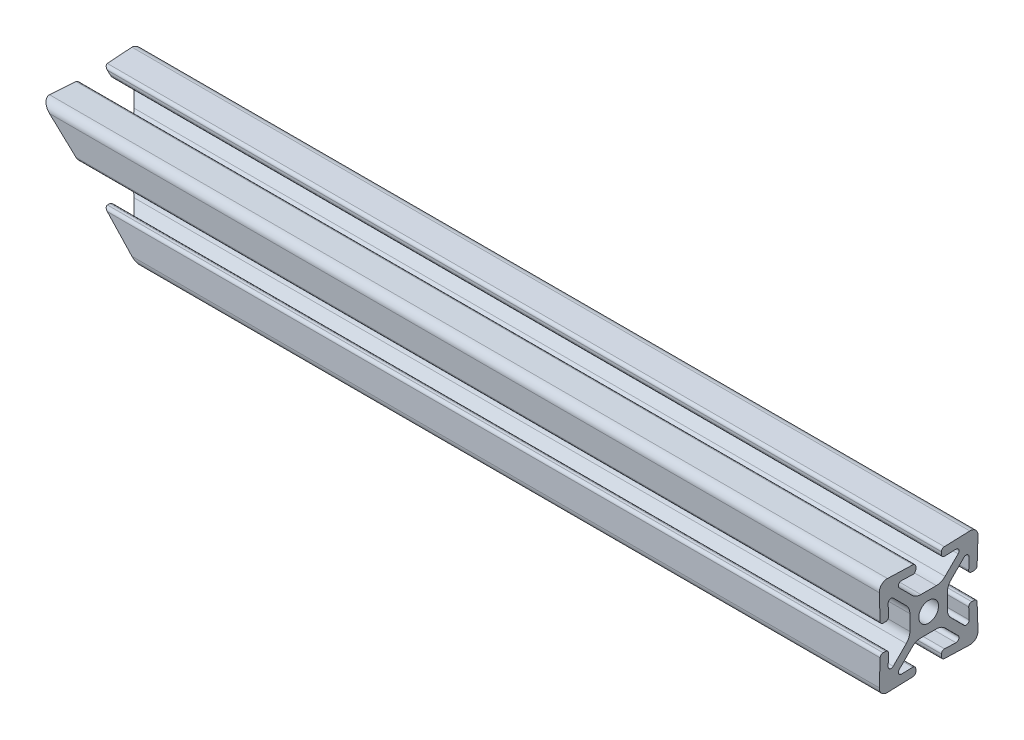
SolidWorks part; units mm, degrees
ref_plane "Front Plane" through (0, 0, 0) normal (0, 0, 1) x (1, 0, 0)
ref_plane "Top Plane" through (0, 0, 0) normal (0, 1, 0) x (1, 0, 0)
ref_plane "Right Plane" through (0, 0, 0) normal (1, 0, 0) x (0, 0, -1)
sketch "Sketch1" plane through (0, 0, 0) normal (1, 0, 0) x (0, 0, -1)
  line L0 (0, -12.7) -> (0, 12.7) construction
  line L1 (-7.874, 12.7) -> (7.874, 12.7) construction
  line L2 (-12.7, 0) -> (12.7, 0) construction
  line L3 (-7.874, 12.7) -> (-7.874, 4.826) construction
  line L4 (-3.302, 12.7) -> (3.302, 12.7) construction
  line L5 (-12.7, -12.7) -> (12.7, -12.7) construction
  line L6 (-12.7, 12.7) -> (12.7, 12.7) construction
  circle A0 centre (0, 0) radius 2.54 construction
  point P7 (0, 12.7)
  point P10 (0, 0)
  point P13 (0, 0)
  point P16 (0, 12.7)
  point P17 (-3.302, 12.7)
  point P18 (3.302, 12.7)
  point P21 (0, -12.7)
  point P24 (0, 12.7)
  dimension "Center Hole Diameter" = 5.08
  dimension "Rail Width" = 25.4
  dimension "Rail Height" = 25.4
  dimension "T-Slot Depth" = 7.874
  dimension "D1" = 15.748
  dimension "T-Slot Width" = 6.604
  dimension "D2" = 12.7
sketch "Sketch2" plane through (0, 0, 0) normal (0, 0, 1) x (1, 0, 0)
  line L0 (-107.7631, 0) -> (107.7631, 0) construction
  line L1 (0, 0) -> (0, 26.104) construction
  line L2 (107.7631, -12.7) -> (107.7631, 12.7) construction
  line L3 (-107.7631, -12.7) -> (-107.7631, 12.7) construction
  point P3 (-69.6631, 0)
  point P8 (0, 0)
  point P9 (69.6631, 0)
  point P12 (107.7631, 0)
  point P15 (-107.7631, 0)
  dimension "Length" = 215.5261
  dimension "D1" = 38.1
  dimension "D2" = 25.4
sketch "Sketch3" plane through (0, 0, 0) normal (1, 0, 0) x (0, 0, -1)
  line L0 (0, 4.826) -> (1.9842, 4.826)
  line L1 (0, -12.7) -> (0, 12.7) construction
  line L2 (4.2293, 5.7559) -> (7.5866, 9.1132)
  line L6 (7.0212, 10.4136) -> (4.0906, 10.3112)
  line L7 (3.302, 11.0728) -> (3.302, 11.7082)
  line L8 (-7.874, 12.7) -> (7.874, 12.7) construction
  line L10 (0, 0) -> (12.7, 12.7) construction
  line L13 (0, 4.826) -> (0, 2.54)
  line L14 (4.826, 0) -> (2.54, 0)
  line L31 (4.826, 0) -> (4.826, 1.9842)
  line L32 (4.0374, 12.4697) -> (10.5971, 12.6988)
  line L33 (-12.7, 0) -> (12.7, 0) construction
  line L34 (-12.7, 12.7) -> (12.7, 12.7) construction
  line L35 (5.7559, 4.2293) -> (9.1132, 7.5866)
  line L36 (0, 12.7) -> (12.7, 12.7) construction
  line L37 (12.7, 12.7) -> (12.7, 8.0234) construction
  line L38 (11.0728, 3.302) -> (11.7082, 3.302)
  line L39 (10.4136, 7.0212) -> (10.3112, 4.0906)
  line L40 (12.6988, 10.5971) -> (12.4697, 4.0374)
  arc A0 (2.54, 0) -> (0, 2.54) centre (0, 0) ccw
  arc A1 (1.9842, 4.826) -> (4.2293, 5.7559) centre (1.9842, 8.001) ccw
  circle A2 centre (0, 0) radius 2.54 construction
  arc A7 (3.302, 11.7082) -> (4.0374, 12.4697) centre (4.064, 11.7082) cw
  arc A8 (4.0906, 10.3112) -> (3.302, 11.0728) centre (4.064, 11.0728) cw
  arc A14 (4.826, 1.9842) -> (5.7559, 4.2293) centre (8.001, 1.9842) cw
  arc A16 (10.5971, 12.6988) -> (12.6988, 10.5971) centre (10.668, 10.668) cw
  arc A17 (7.0212, 10.4136) -> (7.5866, 9.1132) centre (7.0478, 9.652) cw
  arc A18 (10.4136, 7.0212) -> (9.1132, 7.5866) centre (9.652, 7.0478) ccw
  arc A19 (10.3112, 4.0906) -> (11.0728, 3.302) centre (11.0728, 4.064) ccw
  arc A20 (11.7082, 3.302) -> (12.4697, 4.0374) centre (11.7082, 4.064) ccw
  point P37 (3.2994, 4.826)
  point P49 (12.7, 3.302)
  point P52 (3.302, 12.7)
  point P55 (3.302, 10.2837)
  dimension "D4" = 3.175
  dimension "D9" = 2.159
  dimension "D12" = 0.762
  dimension "D3" = 2.032
  dimension "D8" = 0.762
  dimension "D2" = 45
  dimension "D5" = 2
  dimension "D6" = 45
  dimension "D7" = 2.159
extrude "Boss-Extrude1" add sketch "Sketch3" against normal up to vertex (107.7631 mm away) and the other way up to vertex (107.7631 mm away) up to point (-107.7631, 0, 0) other way up to point (107.7631, 0, 0)
mirror "Mirror1" about plane through (0, 0, 0) normal (0, 1, 0) of bodies 104
mirror "Mirror2" about plane through (0, 0, 0) normal (0, 0, 1) of bodies 105
sketch "Sketch4" plane through (-107.7631, 0, 0) normal (-1, 0, 0) x (0, 0, 1)
  line L0 (10.5971, 12.6988) -> (13.4501, 12.6988)
  line L1 (12.6988, 10.5971) -> (12.6988, 12.6988)
  line L2 (12.6988, 12.6988) -> (10.5971, 12.6988)
  line L3 (10.5971, -12.6988) -> (12.6988, -12.6988)
  line L4 (12.6988, -12.6988) -> (12.6988, -10.5971)
ref_plane "Plane1" through (0, 0, 12.6988) normal (0, 0, 1) x (1, 0, 0)
sketch "Sketch5" plane through (0, 0, 12.6988) normal (0, 0, 1) x (1, 0, 0)
  line L0 (-107.7631, -12.7) -> (-82.3631, -12.7)
  line L1 (-107.7631, -12.7) -> (107.7631, -12.7) construction
  line L2 (-82.3631, -12.7) -> (-107.7631, 12.7)
  dimension "D1" = 25.4
extrude "Cut-Extrude1" cut sketch "Sketch5" against normal through all and the other way through all
equation "\"D1@Sketch2\"=\"Rail Height@Sketch1\"*1.5"
equation "\"D2@Sketch2\"=\"Rail Height@Sketch1\""
